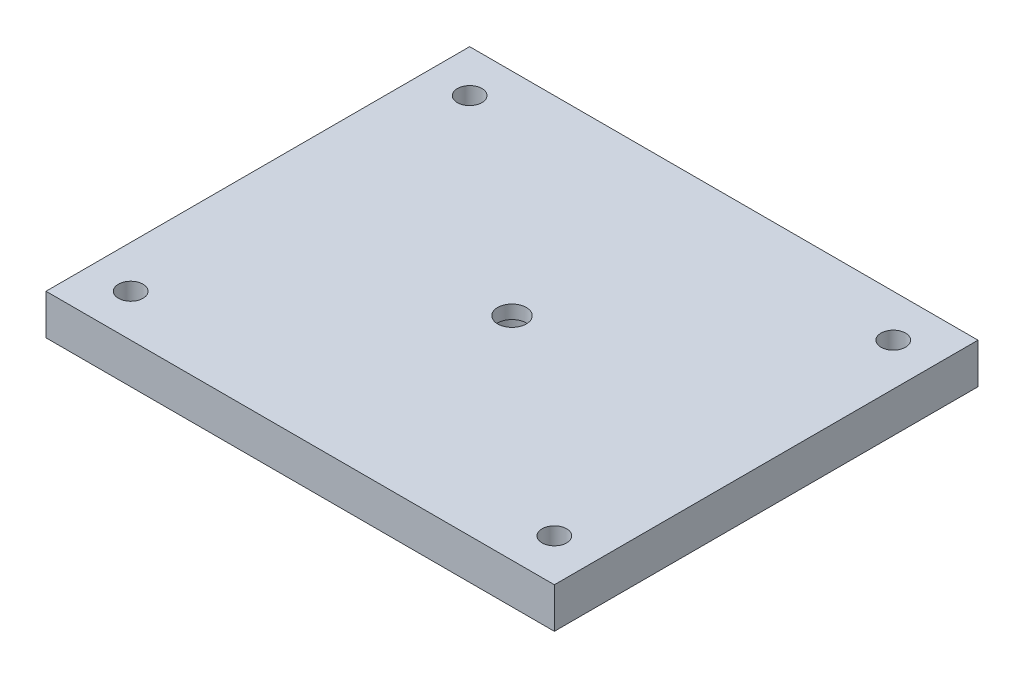
SolidWorks part; units mm, degrees
ref_plane "Front Plane" through (0, 0, 0) normal (0, 0, 1) x (1, 0, 0)
ref_plane "Top Plane" through (0, 0, 0) normal (0, 1, 0) x (1, 0, 0)
ref_plane "Right Plane" through (0, 0, 0) normal (1, 0, 0) x (0, 0, -1)
sketch "Sketch1" plane through (0, 0, 0) normal (0, 1, 0) x (1, 0, 0)
  line L1 (60, -50) -> (-60, -50)
  line L2 (60, -50) -> (60, 50)
  line L3 (60, 50) -> (-60, 50)
  line L4 (-60, -50) -> (-60, 50)
  line L5 (60, -50) -> (-60, 50) construction
  line L6 (60, 50) -> (-60, -50) construction
  dimension "D1" = 100
  dimension "D2" = 120
extrude "Boss-Extrude1" add sketch "Sketch1" along normal blind 9.525
hole_wizard "M5 Clearance Hole1" positions "Sketch2" profile "Sketch3" hole size "M5" standard "ISO" end condition through all
sketch "Sketch2" plane through (0, 9.525, 0) normal (0, 1, 0) x (1, 0, 0)
  line L1 (-50, -40) -> (50, -40)
  line L2 (-50, -40) -> (-50, 40)
  line L3 (-50, 40) -> (50, 40)
  line L4 (50, -40) -> (50, 40)
  line L5 (-50, -40) -> (50, 40) construction
  line L6 (-50, 40) -> (50, -40) construction
  point P0 (-50, -40)
  point P2 (-50, 40)
  point P4 (50, 40)
  point P6 (50, -40)
  dimension "D1" = 100
  dimension "D2" = 80
sketch "Sketch3" plane through (-50, 9.525, 40) normal (1, 0, 0) x (0, 0, 1)
  line L0 (0, 0) -> (0, 9.525)
  line L1 (0, 9.525) -> (2.9, 9.525)
  line L2 (2.9, 9.525) -> (2.9, 0)
  line L5 (2.9, 0) -> (0, 0)
  line L11 (0, -6.35) -> (0, 107.95) construction
  dimension "Thru Hole Dia." = 5.8
  dimension "Thru Hole Depth" = 9.525
hole_wizard "CBORE for 1/4 Socket Head Cap Screw1" positions "Sketch4" profile "Sketch5" counterbore size "1/4" standard "ANSI Inch" end condition through all
sketch "Sketch4" plane through (0, 0, 0) normal (0, -1, 0) x (-1, 0, 0)
  point P0 (0, 0)
sketch "Sketch5" plane through (0, 0, 0) normal (1, 0, 0) x (0, 0, -1)
  line L0 (0, 0) -> (0, 9.525)
  line L1 (0, 9.525) -> (3.3782, 9.525)
  line L3 (3.3782, 9.525) -> (3.3782, 6.35)
  line L4 (3.3782, 6.35) -> (5.5562, 6.35)
  line L5 (5.5562, 6.35) -> (5.5562, 0)
  line L7 (5.5562, 0) -> (0, 0)
  line L11 (0, -6.35) -> (0, 107.95) construction
  dimension "Thru Hole Dia." = 6.7564
  dimension "Thru Hole Depth" = 9.525
  dimension "C'Bore Dia." = 11.1125
  dimension "C'Bore Depth" = 6.35
ref_axis "Axis1" through (0, 13.335, 0) along (0, -1, 0)
